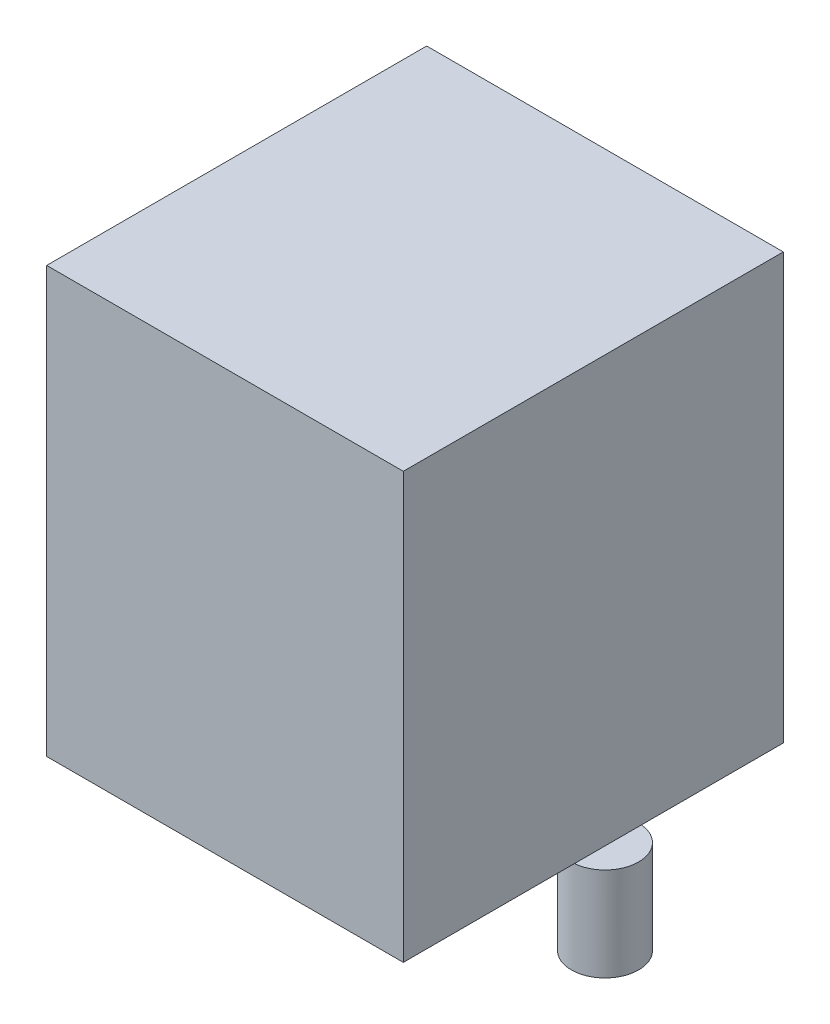
SolidWorks part; units mm, degrees
ref_plane "Front Plane" through (0, 0, 0) normal (0, 0, 1) x (1, 0, 0)
ref_plane "Top Plane" through (0, 0, 0) normal (0, 1, 0) x (1, 0, 0)
ref_plane "Right Plane" through (0, 0, 0) normal (1, 0, 0) x (0, 0, -1)
sketch "Sketch1" plane through (0, 0, 0) normal (0, 1, 0) x (1, 0, 0)
  line L1 (-6.1, 6) -> (6.1, 6)
  line L2 (-6.1, 6) -> (-6.1, -7)
  line L3 (-6.1, -7) -> (6.1, -7)
  line L4 (6.1, 6) -> (6.1, -7)
  circle A0 centre (6, 0) radius 1.15
  circle A1 centre (-6, 0) radius 1.15
  point P4 (0, 6)
  point P10 (0, 0)
  dimension "D2" = 2.3
  dimension "D1" = 6
  dimension "12mm" = 12
  dimension "D3" = 12.2
  dimension "D4" = 13
  dimension "D5" = 6
extrude "Boss-Extrude1" add sketch "Sketch1" against normal blind 3.2 contours L2 A1 | L2 A1 | L4 A0 | L4 A0 region at (-5.5655, 0, 0) region at (-6.5425, 0, 0) region at (6.5425, 0, 0) region at (5.5655, 0, 0)
extrude "Boss-Extrude2" add sketch "Sketch1<3>" along normal blind 14.55 contours A1 L2 L3 L4 A0 L1 | L4 A0 | L2 A1 region at (0, 0, 0.515) region at (-5.5655, 0, 0) region at (5.5655, 0, 0)
sketch "Sketch1<3>" plane through (0, 0, 0) normal (0, 1, 0) x (1, 0, 0) same geometry as "Sketch1"
sketch "Sketch2" plane through (0, 0, 0) normal (0, 0, 1) x (1, 0, 0)
  line L1 (-4.9383, 13.4375) -> (4.9383, 13.4375)
  line L2 (-4.9383, 13.4375) -> (-4.9383, 1.1661)
  line L3 (-4.9383, 1.1661) -> (4.9383, 1.1661)
  line L4 (4.9383, 13.4375) -> (4.9383, 1.1661)
  point P4 (0, 1.1661)
extrude "Cut-Extrude1" cut sketch "Sketch2" along normal blind 2 from surface starting at face at (0, 7.275, -6)
